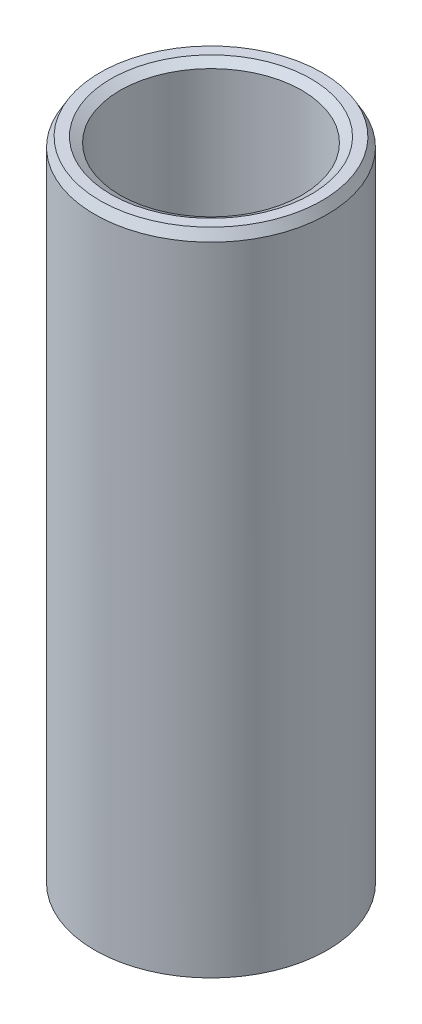
SolidWorks part; units mm, degrees
ref_plane "Front Plane" through (0, 0, 0) normal (0, 0, 1) x (1, 0, 0)
ref_plane "Top Plane" through (0, 0, 0) normal (0, 1, 0) x (1, 0, 0)
ref_plane "Right Plane" through (0, 0, 0) normal (1, 0, 0) x (0, 0, -1)
sketch "Sketch1" plane through (0, 0, 0) normal (0, 1, 0) x (1, 0, 0)
  circle A0 centre (0, 0) radius 30
  dimension "SLEEVE_OD" = 60
extrude "Boss-Extrude1" add sketch "Sketch1" along normal blind 168.1035
sketch "Sketch2" plane through (0, 0, 0) normal (0, 1, 0) x (1, 0, 0)
  circle A0 centre (0, 0) radius 23.4314
  dimension "BORE_D" = 46.8628
extrude "Cut-Extrude1" cut sketch "Sketch2" along normal through all
chamfer "Chamfer1" distance 2.3863 angle 30 4 edges at (0, 168.1035, 23.4314) (0, 0, 23.4314) (0, 0, 30) (0, 168.1035, 30) first distance on face at (0, 168.1035, 23.4314) first distance on face at (0, 0, 23.4314) first distance on face at (0, 168.1035, 30)
